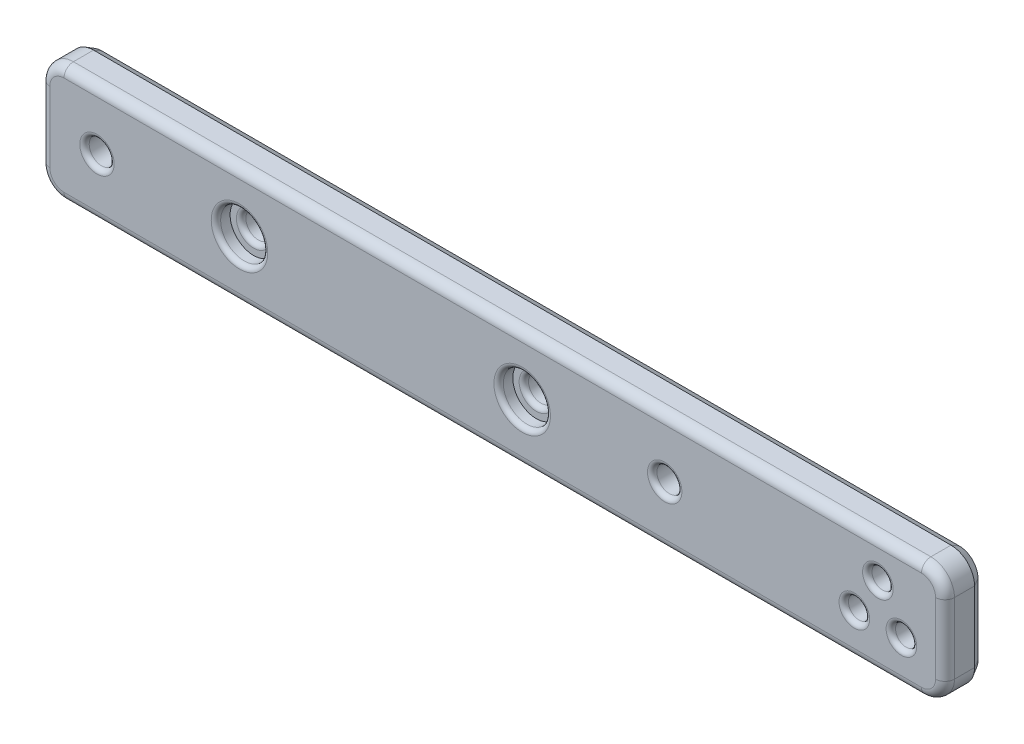
SolidWorks part; units mm, degrees
ref_plane "Front Plane" through (0, 0, 0) normal (0, 0, 1) x (1, 0, 0)
ref_plane "Top Plane" through (0, 0, 0) normal (0, 1, 0) x (1, 0, 0)
ref_plane "Right Plane" through (0, 0, 0) normal (1, 0, 0) x (0, 0, -1)
sketch "Sketch2" plane through (0, 0, 0) normal (0, 0, 1) x (1, 0, 0)
  line L1 (-96, -12.5) -> (96, -12.5)
  line L2 (-96, -12.5) -> (-96, 12.5)
  line L3 (-96, 12.5) -> (96, 12.5)
  line L4 (96, -12.5) -> (96, 12.5)
  line L5 (-96, -12.5) -> (96, 12.5) construction
  line L6 (-96, 12.5) -> (96, -12.5) construction
  point P0 (0, 0)
  dimension "D1" = 192
  dimension "D2" = 25
extrude "Boss-Extrude1" add sketch "Sketch2" along normal blind 8
sketch "Sketch3" plane through (0, 0, 8) normal (0, 0, 1) x (1, 0, 0)
  line L0 (-96, 12.5) -> (-96, -12.5) construction
  line L1 (-84, 0) -> (-53.75, 0) construction
  line L2 (6.25, 0) -> (36.5, 0) construction
  line L4 (86.75, -3.5) -> (76.75, -3.5) construction
  line L5 (81.75, 4.5) -> (81.75, -3.5) construction
  line L6 (6.25, 0) -> (-53.75, 0) construction
  line L8 (96, 12.5) -> (-96, 12.5) construction
  circle A0 centre (-84, 0) radius 2.65
  circle A1 centre (36.5, 0) radius 2.65
  circle A2 centre (76.75, -3.5) radius 2.25
  circle A3 centre (86.75, -3.5) radius 2.25
  circle A4 centre (81.75, 4.5) radius 2.25
  circle A5 centre (-53.75, 0) radius 2.65
  circle A6 centre (6.25, 0) radius 2.65
  point P14 (81.75, 8.9107)
  dimension "D1" = 5.3
  dimension "D2" = 5.3
  dimension "D10" = 4.5
  dimension "D3" = 12
  dimension "D4" = 120.5
  dimension "D5" = 8
  dimension "D6" = 60
  dimension "D7" = 8
  dimension "D8" = 10
  dimension "D9" = 165.75
extrude "Cut-Extrude1" cut sketch "Sketch3" against normal through all
sketch "Sketch4" plane through (0, 0, 8) normal (0, 0, 1) x (1, 0, 0)
  circle A0 centre (-53.75, 0) radius 5
  circle A1 centre (6.25, 0) radius 5
  dimension "D1" = 10
extrude "Cut-Extrude2" cut sketch "Sketch4" against normal blind 3
fillet "Fillet1" radius 5 4 edges at (-96, -12.5, 4) (-96, 12.5, 4) (96, -12.5, 4) (96, 12.5, 4)
fillet "Fillet2" radius 2 8 edges at (94.5355, 11.0355, 8) (96, 0, 8) (94.5355, -11.0355, 8) (0, -12.5, 8) (-94.5355, -11.0355, 8) (-96, 0, 8) (-94.5355, 11.0355, 8) (0, 12.5, 8)
fillet "Fillet3" radius 1 9 edges at (84, 4.5, 8) (89, -3.5, 8) (79, -3.5, 8) (39.15, 0, 8) (-81.35, 0, 8) (8.9, 0, 5) (-51.1, 0, 5) (11.25, 0, 8) (-48.75, 0, 8)
chamfer "Chamfer1" distance 1 angle 60 8 edges at (0, 12.5, 0) (-94.5355, 11.0355, 0) (94.5355, 11.0355, 0) (-96, 0, 0) (96, 0, 0) (-94.5355, -11.0355, 0) (94.5355, -11.0355, 0) (0, -12.5, 0) first distance on face at (-81.35, 0, 0)
chamfer "Chamfer2" distance 1 angle 30 7 edges at (89, -3.5, 0) (84, 4.5, 0) (79, -3.5, 0) (39.15, 0, 0) (8.9, 0, 0) (-51.1, 0, 0) (-81.35, 0, 0) first distance on face at (84.5, -3.5, 7) first distance on face at (79.5, 4.5, 7) first distance on face at (74.5, -3.5, 7) first distance on face at (33.85, 0, 7) first distance on face at (8.9, 0, 4) first distance on face at (-51.1, 0, 4) first distance on face at (-86.65, 0, 7)
ref_axis "Axis1" through (-53.75, 0, 1) along (0, 0, 1)
ref_axis "Axis2" through (6.25, 0, 1) along (0, 0, 1)
ref_plane "Plane1" through (6.25, 0, 0) normal (1, 0, 0) x (0, 0, -1)
ref_plane "Plane2" through (-53.75, 0, 0) normal (1, 0, 0) x (0, 0, -1)
ref_plane "Plane3" through (-23.75, 0, 0) normal (1, 0, 0) x (0, 0, -1)
